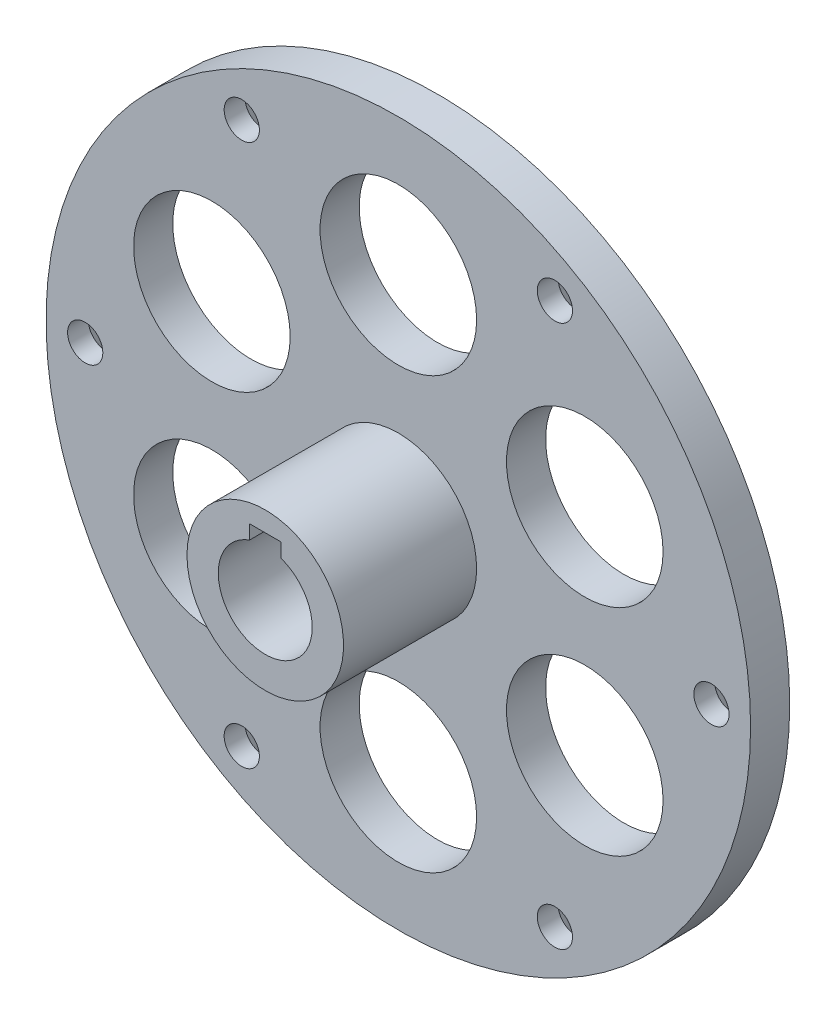
SolidWorks part; units mm, degrees
material "7079 Alloy"
ref_plane "Front Plane" through (0, 0, 0) normal (0, 0, 1) x (1, 0, 0)
ref_plane "Top Plane" through (0, 0, 0) normal (0, 1, 0) x (1, 0, 0)
ref_plane "Right Plane" through (0, 0, 0) normal (1, 0, 0) x (0, 0, -1)
sketch "Sketch1" plane through (0, 0, 0) normal (0, 0, 1) x (1, 0, 0)
  circle A0 centre (0, 0) radius 45
  circle A1 centre (0, 0) radius 6
  dimension "D1" = 12
  dimension "D2" = 90
extrude "Extrude1" add sketch "Sketch1" along normal blind 5
sketch "Sketch2" plane through (0, 0, 0) normal (0, 0, -1) x (-1, 0, 0)
  circle A0 centre (0, 0) radius 6 construction
  circle A1 centre (0, 0) radius 6
  circle A2 centre (0, 0) radius 10
  dimension "D1" = 20
extrude "Extrude2" add sketch "Sketch2" against normal blind 22
ref_axis "Axis1" through (0, 0, 22) along (0, 0, -1)
sketch "Sketch4" plane through (0, 0, 5) normal (0, 0, 1) x (1, 0, 0)
  line L0 (0, 0) -> (0, 27.5) construction
  line L2 (0, 0) -> (0, -27.5) construction
  circle A0 centre (23.8157, 13.75) radius 10
  circle A1 centre (0, 27.5) radius 10
  circle A2 centre (23.8157, -13.75) radius 10
  circle A3 centre (0, -27.5) radius 10
  circle A4 centre (-23.8157, -13.75) radius 10
  circle A5 centre (-23.8157, 13.75) radius 10
  circle A11 centre (0, 0) radius 27.5 construction
  dimension "D2" = 20
  dimension "D3" = 55
extrude "Cut-Extrude2" cut sketch "Sketch4" against normal blind 100
sketch "Sketch5" plane through (0, 0, 22) normal (0, 0, 1) x (1, 0, 0)
  line L0 (0, 6) -> (0, 7.4569) construction
  line L1 (2, 7.4569) -> (2, 5.6569)
  line L2 (2, 7.4569) -> (-2, 7.4569)
  line L4 (2, 5.6569) -> (-2, 5.6569)
  line L5 (-2, 7.4569) -> (-2, 5.6569)
  circle A0 centre (0, 0) radius 6 construction
  point P12 (0, 5.6569)
  dimension "D1" = 4
  dimension "D2" = 1.8
extrude "Cut-Extrude3" cut sketch "Sketch5" against normal blind 50
sketch "Sketch6" plane through (0, 0, 0) normal (0, 0, -1) x (-1, 0, 0)
  line L0 (0, 27.5) -> (23.8157, 13.75) construction
  line L1 (0, 0) -> (11.9078, 20.625) construction
  line L2 (11.9078, 20.625) -> (20, 34.641) construction
  circle A0 centre (20, 34.641) radius 2
  dimension "D1" = 40
  dimension "D2" = 4
extrude "Cut-Extrude4" cut sketch "Sketch6" against normal blind 15
hole_wizard "CSK for M4 Hex Socket Countersunk Head Screw1" positions "3DSketch1" profile "Sketch7" countersink size "M4" standard "DIN" end condition through all
sketch3d "3DSketch1"
  line L0 (-20, 34.641, 5) -> (-20, 34.641, 0) construction
  point P0 (-20, 34.641, 0)
sketch "Sketch7" plane through (-20, 34.641, 0) normal (1, 0, 0) x (0, 1, 0)
  line L0 (0, 0) -> (0, 22)
  line L1 (0, 22) -> (2.25, 22)
  line L2 (2.25, 22) -> (2.25, 2.34)
  line L3 (2.25, 2.34) -> (4.59, 0)
  line L5 (4.59, 0) -> (0, 0)
  line L6 (-2.25, 2.34) -> (-4.59, 0) construction
  line L11 (0, -6.35) -> (0, 107.95) construction
  dimension "Thru Hole Dia." = 4.5
  dimension "Thru Hole Depth" = 22
  dimension "Near C'Sink Dia." = 9.18
  dimension "Near C'Sink Angle" = 90
pattern_circular "CirPattern1" count 6 over 360 about axis through (0, 0, 22) along (0, 0, -1) of "CSK for M4 Hex Socket Countersunk Head Screw1"
